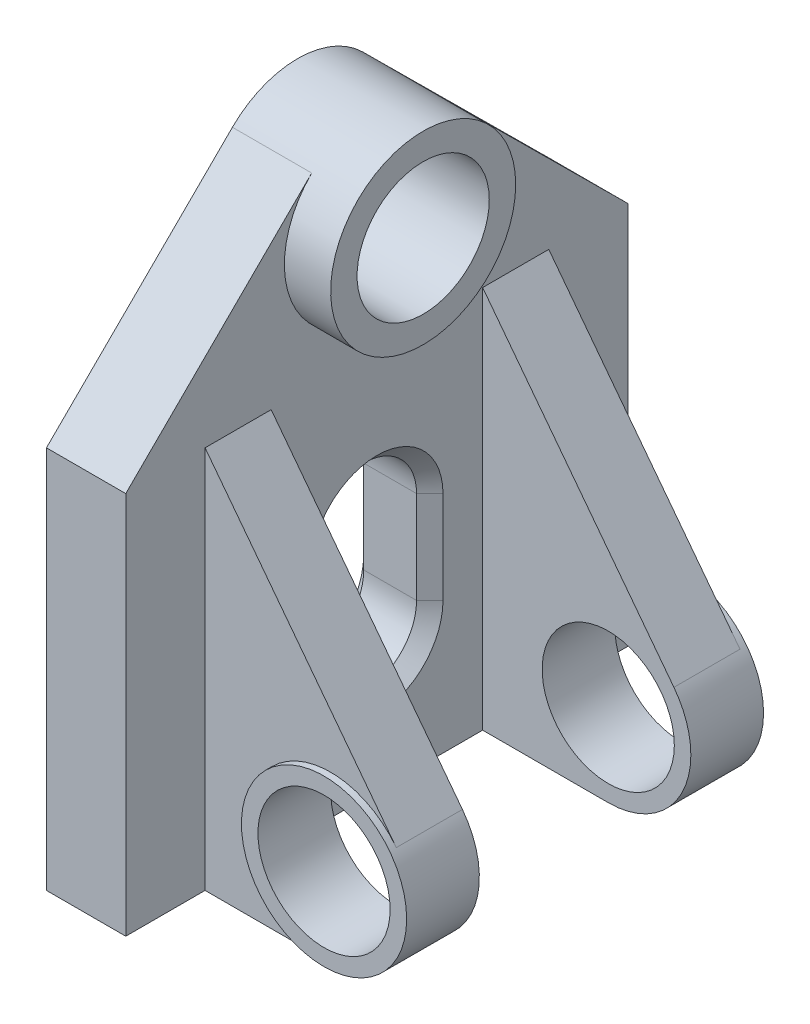
SolidWorks part; units mm, degrees
ref_plane "Front Plane" through (0, 0, 0) normal (0, 0, 1) x (1, 0, 0)
ref_plane "Top Plane" through (0, 0, 0) normal (0, 1, 0) x (1, 0, 0)
ref_plane "Right Plane" through (0, 0, 0) normal (1, 0, 0) x (0, 0, -1)
sketch "Sketch1" plane through (0, 0, 0) normal (1, 0, 0) x (0, 0, -1)
  line L0 (0, 0) -> (25218.4942, 0) construction
  line L1 (0, 0) -> (0, 25218.4942) construction
  line L2 (38, 58) -> (9.8639, 85.9349)
  line L3 (-38, 0) -> (38, 0)
  line L4 (-38, 0) -> (-38, 58)
  line L5 (-38, 58) -> (38, 58) construction
  line L6 (38, 0) -> (38, 58)
  line L7 (-38, 58) -> (-9.8639, 85.9349)
  line L8 (0, 34) -> (0, 20) construction
  line L9 (8, 34) -> (8, 20)
  line L10 (-8, 34) -> (-8, 20)
  circle A0 centre (0, 76) radius 10
  circle A1 centre (0, 76) radius 14
  arc A2 (8, 34) -> (-8, 34) centre (0, 34) ccw
  arc A3 (-8, 20) -> (8, 20) centre (0, 20) ccw
  point P16 (0, 27)
  point P23 (19.6758, 9.0113)
  dimension "D3" = 20
  dimension "D4" = 28
  dimension "D6" = 8
  dimension "D1" = 76
  dimension "D2" = 58
  dimension "D5" = 76
  dimension "D7" = 14
  dimension "D8" = 20
extrude "Boss-Extrude1" add sketch "Sketch1" along normal blind 12 contours A1 L7 L4 L3 L6 L2 A3 L10 A2 L9 region at (0, 29, -36.8528)
extrude "Boss-Extrude2" add sketch "Sketch1<3>" along normal blind 19 contours A1 A0 region at (0, 81.2286, -12.5591)
sketch "Sketch1<3>" plane through (0, 0, 0) normal (1, 0, 0) x (0, 0, -1) same geometry as "Sketch1"
sketch "Sketch2" plane through (0, 0, 0) normal (0, 0, 1) x (1, 0, 0)
  line L0 (12, 0) -> (0, 0) construction
  line L1 (12, 0) -> (31, 0)
  line L2 (12, 58) -> (40.9368, 20.0835)
  line L3 (12, 0) -> (12, 58) construction
  line L4 (12, 58) -> (12, 0)
  circle A0 centre (31, 12.5) radius 12.5
  circle A1 centre (31, 12.5) radius 10
  dimension "D1" = 25
  dimension "D2" = 20
  dimension "D3" = 19
extrude "Boss-Extrude3" add sketch "Sketch2" along normal blind 10 from offset 16 contours A0 L2 L4 L1 region at (19.3405, 27.6065, 0)
extrude "Boss-Extrude4" add sketch "Sketch2<4>" along normal blind 11 from offset 16 contours A0 A1 region at (20.1132, 17.8865, 0)
sketch "Sketch2<4>" plane through (0, 0, 0) normal (0, 0, 1) x (1, 0, 0) same geometry as "Sketch2"
mirror "Mirror2" about plane through (0, 0, 0) normal (0, 0, 1) of "Boss-Extrude4", "Boss-Extrude3"
chamfer "Chamfer1" distance 2 angle 45 8 edges at (0, 42, 0) (0, 27, -8) (0, 12, 0) (0, 27, 8) (12, 42, 0) (12, 27, 8) (12, 27, -8) (12, 12, 0)
